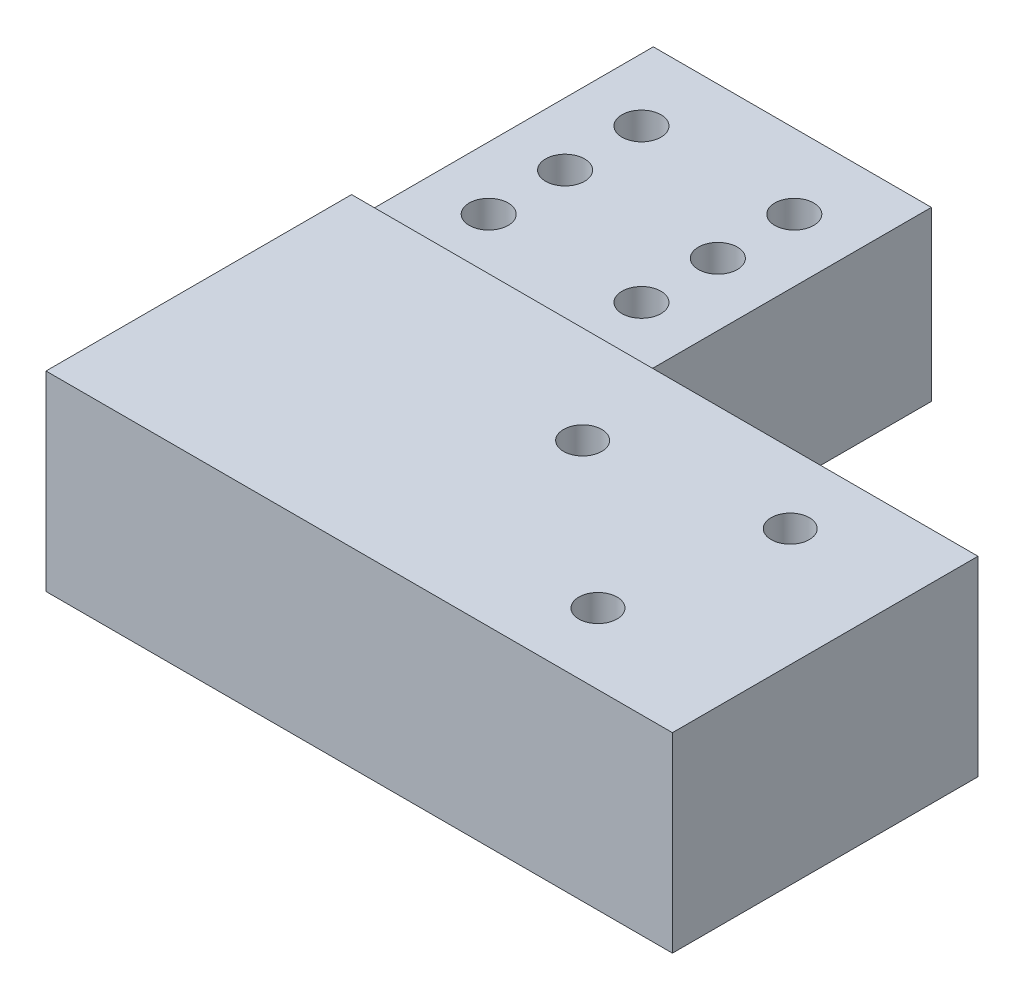
SolidWorks part; units mm, degrees
ref_plane "Front Plane" through (0, 0, 0) normal (0, 0, 1) x (1, 0, 0)
ref_plane "Top Plane" through (0, 0, 0) normal (0, 1, 0) x (1, 0, 0)
ref_plane "Right Plane" through (0, 0, 0) normal (1, 0, 0) x (0, 0, -1)
sketch "Sketch1" plane through (0, 0, 0) normal (0, 1, 0) x (1, 0, 0)
  line L1 (0, 0) -> (36.4, 0)
  line L2 (0, 0) -> (0, 39.5)
  line L3 (0, 39.5) -> (36.4, 39.5)
  line L4 (36.4, 0) -> (36.4, 39.5)
  circle A0 centre (8.2, 29.75) radius 2.55
  circle A1 centre (28.2, 29.75) radius 2.55
  circle A2 centre (28.2, 19.75) radius 2.55
  circle A3 centre (28.2, 9.75) radius 2.55
  circle A4 centre (8.2, 19.75) radius 2.55
  circle A5 centre (8.2, 9.75) radius 2.55
  dimension "D3" = 5.1
  dimension "D1" = 8.2
  dimension "D2" = 9.75
  dimension "D4" = 8.2
  dimension "D5" = 9.75
  dimension "D8" = 20
  dimension "D9" = 39.5
  dimension "D6" = 2
  dimension "D7" = 3
extrude "Boss-Extrude1" add sketch "Sketch1" along normal blind 22
sketch "Sketch2" plane through (0, 22, 0) normal (0, 1, 0) x (1, 0, 0)
  line L1 (0, 39.5) -> (82, 39.5)
  line L2 (0, 39.5) -> (0, 79.5)
  line L3 (0, 79.5) -> (82, 79.5)
  line L4 (82, 39.5) -> (82, 79.5)
  dimension "D1" = 82
  dimension "D2" = 40
extrude "Boss-Extrude2" add sketch "Sketch2" against normal blind 22 and the other way blind 3
mirror "Mirror3" about plane through (0, 22, 0) normal (0, 0, -1) of "Boss-Extrude1", "Boss-Extrude2"
sketch "Sketch7" plane through (0, 25, 0) normal (0, 1, 0) x (1, 0, 0)
  line L0 (66.5819, -48.6599) -> (42.9961, -52.2457)
  line L1 (42.9961, -52.2457) -> (66.5819, -52.2457)
  line L2 (66.5819, -52.2457) -> (66.5819, -48.6599)
  line L3 (42.9961, -52.2457) -> (62.9961, -70.2457)
  line L4 (62.9961, -70.2457) -> (62.9961, -52.2457)
  line L5 (62.9961, -52.2457) -> (42.9961, -52.2457)
  line L6 (66.5819, -48.6599) -> (66.5819, -39.5)
  line L7 (0, -39.5) -> (82, -39.5) construction
  line L8 (66.5819, -39.5) -> (66.5819, -48.6599)
  line L9 (66.5819, -48.6599) -> (82, -48.6599)
  line L10 (82, -39.5) -> (82, -79.5) construction
  dimension "D5" = 9.1599
  dimension "D1" = 18
  dimension "D2" = 23.5858
  dimension "D3" = 3.5858
  dimension "D4" = 3.5858
  dimension "D6" = 15.4181
hole_wizard "Ø5.0mm Dowel Hole1" positions "3DSketch1" profile "Sketch8" hole size "Ø5.0" standard "ANSI Metric" end condition through all
sketch3d "3DSketch1"
  point P0 (42.9961, 25, 52.2457)
  point P3 (62.9961, 25, 70.2457)
  point P7 (66.5819, 25, 48.6599)
sketch "Sketch8" plane through (42.9961, 25, 52.2457) normal (1, 0, 0) x (0, 0, 1)
  line L0 (0, 0) -> (0, 25)
  line L1 (0, 25) -> (2.5, 25)
  line L2 (2.5, 25) -> (2.5, 0)
  line L5 (2.5, 0) -> (0, 0)
  line L11 (0, -6.35) -> (0, 107.95) construction
  dimension "Thru Hole Dia." = 5
  dimension "Thru Hole Depth" = 25
sketch "Sketch9" plane through (0, 25, 0) normal (0, 1, 0) x (1, 0, 0)
  line L0 (66.5819, -48.6599) -> (66.5819, -39.5)
  line L1 (0, -39.5) -> (82, -39.5) construction
  line L2 (66.5819, -39.5) -> (82, -39.5)
sketch "Sketch3" plane through (0, 22, 0) normal (0, 1, 0) x (1, 0, 0)
  line L1 (0, 39.5) -> (0, -39.5) construction
  line L4 (0, 0) -> (85.7109, 0)
  line L5 (0, 0) -> (0, 93.142)
  line L6 (0, 93.142) -> (85.7109, 93.142)
  line L7 (85.7109, 0) -> (85.7109, 93.142)
  dimension "D1" = 85.7109
  dimension "D2" = 93.142
extrude "Cut-Extrude1" cut sketch "Sketch3" against normal blind 50 and the other way blind 30
